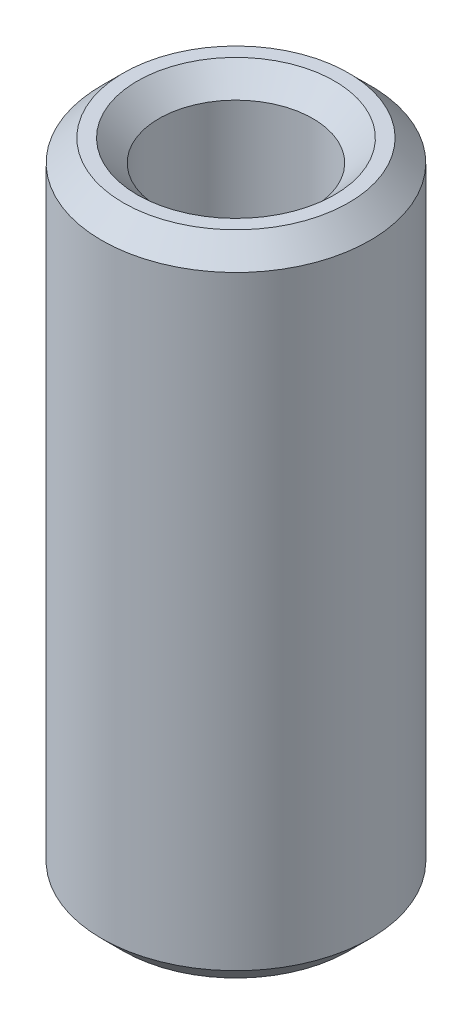
SolidWorks part; units mm, degrees
ref_plane "Front Plane" through (0, 0, 0) normal (0, 0, 1) x (1, 0, 0)
ref_plane "Top Plane" through (0, 0, 0) normal (0, 1, 0) x (1, 0, 0)
ref_plane "Right Plane" through (0, 0, 0) normal (1, 0, 0) x (0, 0, -1)
sketch "Sketch1" plane through (0, 0, 0) normal (0, 1, 0) x (1, 0, 0)
  circle A0 centre (0, 0) radius 7.5
  dimension "SLEEVE_OD" = 15
extrude "Boss-Extrude1" add sketch "Sketch1" along normal blind 36.2069
sketch "Sketch2" plane through (0, 0, 0) normal (0, 1, 0) x (1, 0, 0)
  circle A0 centre (0, 0) radius 4.2991
  dimension "BORE_D" = 8.5982
extrude "Cut-Extrude1" cut sketch "Sketch2" along normal through all
chamfer "Chamfer1" distance 1.2106 angle 45 4 edges at (0, 36.2069, 4.2991) (0, 0, 4.2991) (0, 0, 7.5) (0, 36.2069, 7.5)
